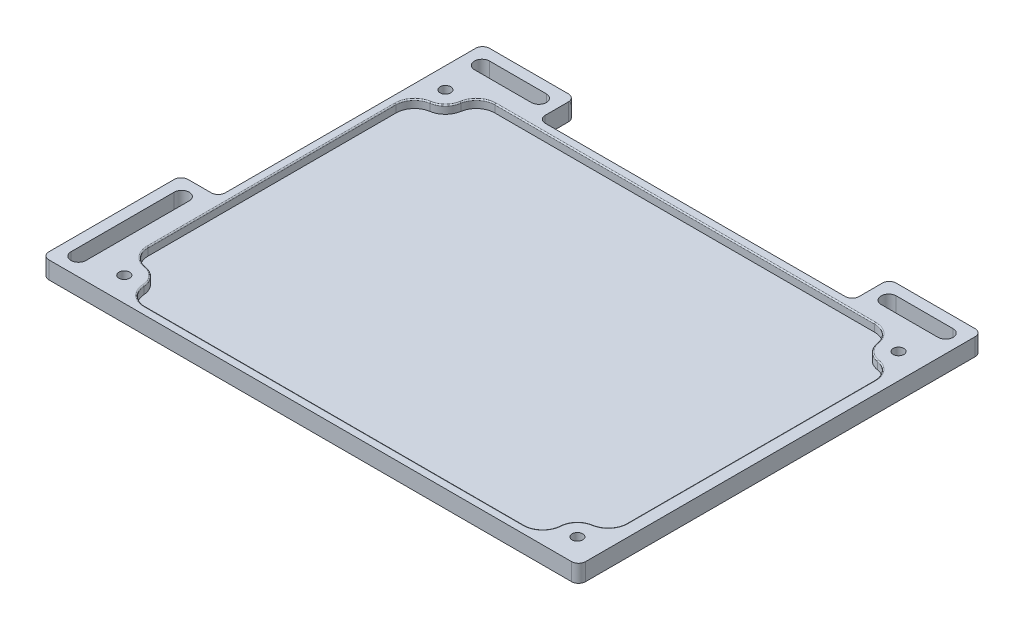
SolidWorks part; units mm, degrees
ref_plane "Front Plane" through (0, 0, 0) normal (0, 0, 1) x (1, 0, 0)
ref_plane "Top Plane" through (0, 0, 0) normal (0, 1, 0) x (1, 0, 0)
ref_plane "Right Plane" through (0, 0, 0) normal (1, 0, 0) x (0, 0, -1)
sketch "Sketch1" plane through (0, 0, 0) normal (0, 1, 0) x (1, 0, 0)
  line L1 (0, 0) -> (208.28, 0) construction
  line L2 (0, 0) -> (0, 150.9) construction
  line L3 (0, 150.9) -> (208.28, 150.9) construction
  line L4 (208.28, 0) -> (208.28, 150.9) construction
  line L5 (-3.5, -3.5) -> (211.78, -3.5)
  line L6 (-3.5, -3.5) -> (-3.5, 154.4)
  line L7 (-3.5, 154.4) -> (211.78, 154.4)
  line L8 (211.78, -3.5) -> (211.78, 154.4)
  circle A0 centre (5.5, 145.4) radius 2.3
  circle A1 centre (5.5, 7) radius 2.3
  circle A2 centre (200.78, 7) radius 2.3
  circle A3 centre (200.78, 145.4) radius 2.3
  point P17 (0, 0)
  dimension "D7" = 4.6
  dimension "D1" = 208.28
  dimension "D2" = 5.5
  dimension "D3" = 3.5
  dimension "D4" = 3.5
  dimension "D5" = 3.5
  dimension "D6" = 3.5
  dimension "D10" = 5.5
  dimension "D11" = 7
extrude "Boss-Extrude1" add sketch "Sketch1" along normal blind 7.5
extrude "Boss-Extrude2" add sketch "Sketch1<2>" along normal blind 2 from surface contours A3 | A1 | A0 | A2 region at (200.78, 0, -145.4) starting at face at (200.78, 0, -4.7)
sketch "Sketch1<2>" plane through (0, 0, 0) normal (0, 1, 0) x (1, 0, 0) same geometry as "Sketch1"
sketch "Sketch2" plane through (0, 7.5, 0) normal (0, 1, 0) x (1, 0, 0)
  line L0 (21.3035, 150.9) -> (184.9765, 150.9)
  line L1 (206.28, 129.5965) -> (206.28, 22.8035)
  line L2 (184.8113, 0) -> (21.4687, 0)
  line L3 (0, 129.5965) -> (0, 22.8035)
  line L6 (0, 0) -> (208.28, 0) construction
  line L7 (0, 150.9) -> (208.28, 150.9) construction
  line L9 (0, 0) -> (0, 150.9) construction
  arc A0 (6.75, 137.4983) -> (13.4017, 144.15) centre (5.5, 145.4) ccw
  arc A1 (13.4844, 7.5) -> (6.75, 14.9017) centre (5.5, 7) ccw
  arc A2 (192.8783, 144.15) -> (199.53, 137.4983) centre (200.78, 145.4) ccw
  arc A3 (199.53, 14.9017) -> (192.7956, 7.5) centre (200.78, 7) ccw
  arc A4 (184.8113, 0) -> (192.7956, 7.5) centre (184.8113, 8) ccw
  arc A5 (206.28, 22.8035) -> (199.53, 14.9017) centre (198.28, 22.8035) cw
  arc A6 (206.28, 129.5965) -> (199.53, 137.4983) centre (198.28, 129.5965) ccw
  arc A7 (184.9765, 150.9) -> (192.8783, 144.15) centre (184.9765, 142.9) cw
  arc A8 (0, 22.8035) -> (6.75, 14.9017) centre (8, 22.8035) ccw
  arc A9 (0, 129.5965) -> (6.75, 137.4983) centre (8, 129.5965) cw
  arc A10 (21.3035, 150.9) -> (13.4017, 144.15) centre (21.3035, 142.9) ccw
  arc A11 (21.4687, 0) -> (13.4844, 7.5) centre (21.4687, 8) cw
  point P28 (206.28, 12.8095)
  point P35 (0, 12.8095)
  dimension "D1" = 16
  dimension "D2" = 16
  dimension "D3" = 16
  dimension "D4" = 16
  dimension "D7" = 8
  dimension "D8" = 8
extrude "Cut-Extrude1" cut sketch "Sketch2" against normal blind 3.5
sketch "Sketch3" plane through (0, 7.5, 0) normal (0, 1, 0) x (1, 0, 0)
  line L0 (-11.5, 48.75) -> (-11.5, 4.25) construction
  line L1 (-3.5, -3.5) -> (-19.5, -3.5)
  line L2 (-3.5, -3.5) -> (-3.5, 56.5)
  line L3 (-3.5, 56.5) -> (-19.5, 56.5)
  line L4 (-19.5, -3.5) -> (-19.5, 56.5)
  line L5 (-8.25, 48.75) -> (-8.25, 4.25)
  line L6 (-14.75, 48.75) -> (-14.75, 4.25)
  line L7 (4.25, 162.4) -> (28.75, 162.4) construction
  line L8 (-3.5, 154.4) -> (36.5, 154.4)
  line L9 (-3.5, 154.4) -> (-3.5, 170.4)
  line L10 (-3.5, 170.4) -> (36.5, 170.4)
  line L11 (36.5, 154.4) -> (36.5, 170.4)
  line L12 (4.25, 165.65) -> (28.75, 165.65)
  line L13 (4.25, 159.15) -> (28.75, 159.15)
  line L14 (179.53, 162.4) -> (204.03, 162.4) construction
  line L15 (211.78, 154.4) -> (171.78, 154.4)
  line L16 (211.78, 154.4) -> (211.78, 170.4)
  line L17 (211.78, 170.4) -> (171.78, 170.4)
  line L18 (171.78, 154.4) -> (171.78, 170.4)
  line L19 (179.53, 165.65) -> (204.03, 165.65)
  line L20 (179.53, 159.15) -> (204.03, 159.15)
  arc A0 (-8.25, 48.75) -> (-14.75, 48.75) centre (-11.5, 48.75) ccw
  arc A1 (-14.75, 4.25) -> (-8.25, 4.25) centre (-11.5, 4.25) ccw
  arc A2 (4.25, 165.65) -> (4.25, 159.15) centre (4.25, 162.4) ccw
  arc A3 (28.75, 159.15) -> (28.75, 165.65) centre (28.75, 162.4) ccw
  arc A4 (179.53, 165.65) -> (179.53, 159.15) centre (179.53, 162.4) ccw
  arc A5 (204.03, 159.15) -> (204.03, 165.65) centre (204.03, 162.4) ccw
  point P7 (-11.5, 26.5)
  point P12 (-11.5, 1)
  point P14 (-11.5, 52)
  point P21 (16.5, 162.4)
  point P26 (32, 162.4)
  point P27 (1, 162.4)
  point P36 (191.78, 162.4)
  point P41 (176.28, 162.4)
  point P42 (207.28, 162.4)
  dimension "D1" = 60
  dimension "D2" = 16
  dimension "D3" = 4.5
  dimension "D4" = 8
  dimension "D5" = 4.5
  dimension "D6" = 6.5
  dimension "D7" = 40
  dimension "D8" = 16
  dimension "D9" = 6.5
  dimension "D10" = 8
  dimension "D11" = 4.5
  dimension "D12" = 4.5
  dimension "D13" = 40
  dimension "D14" = 16
  dimension "D15" = 6.5
  dimension "D16" = 4.5
  dimension "D17" = 4.5
extrude "Boss-Extrude3" add sketch "Sketch3" against normal up to surface (7.5 mm away) up to face at (104.14, 0, -75.45)
fillet "Fillet1" radius 0.5 16 edges at (190.1727, 7.5, -148.9828) (195.1231, 7.5, -139.7431) (204.3628, 7.5, -134.7927) (206.28, 7.5, -76.2) (204.3628, 7.5, -17.6073) (194.8627, 7.5, -12.3838) (190.2885, 7.5, -2.169) (103.14, 7.5, 0) (15.9915, 7.5, -2.169) (11.4173, 7.5, -12.3838) (1.9172, 7.5, -17.6073) (0, 7.5, -76.2) (1.9172, 7.5, -134.7927) (11.1569, 7.5, -139.7431) (16.1073, 7.5, -148.9828) (103.14, 7.5, -150.9)
fillet "Fillet2" radius 3 10 edges at (211.78, 3.75, 3.5) (171.78, 3.75, -170.4) (171.78, 3.75, -154.4) (211.78, 3.75, -170.4) (36.5, 3.75, -154.4) (36.5, 3.75, -170.4) (-3.5, 3.75, -170.4) (-3.5, 3.75, -56.5) (-19.5, 3.75, -56.5) (-19.5, 3.75, 3.5)
